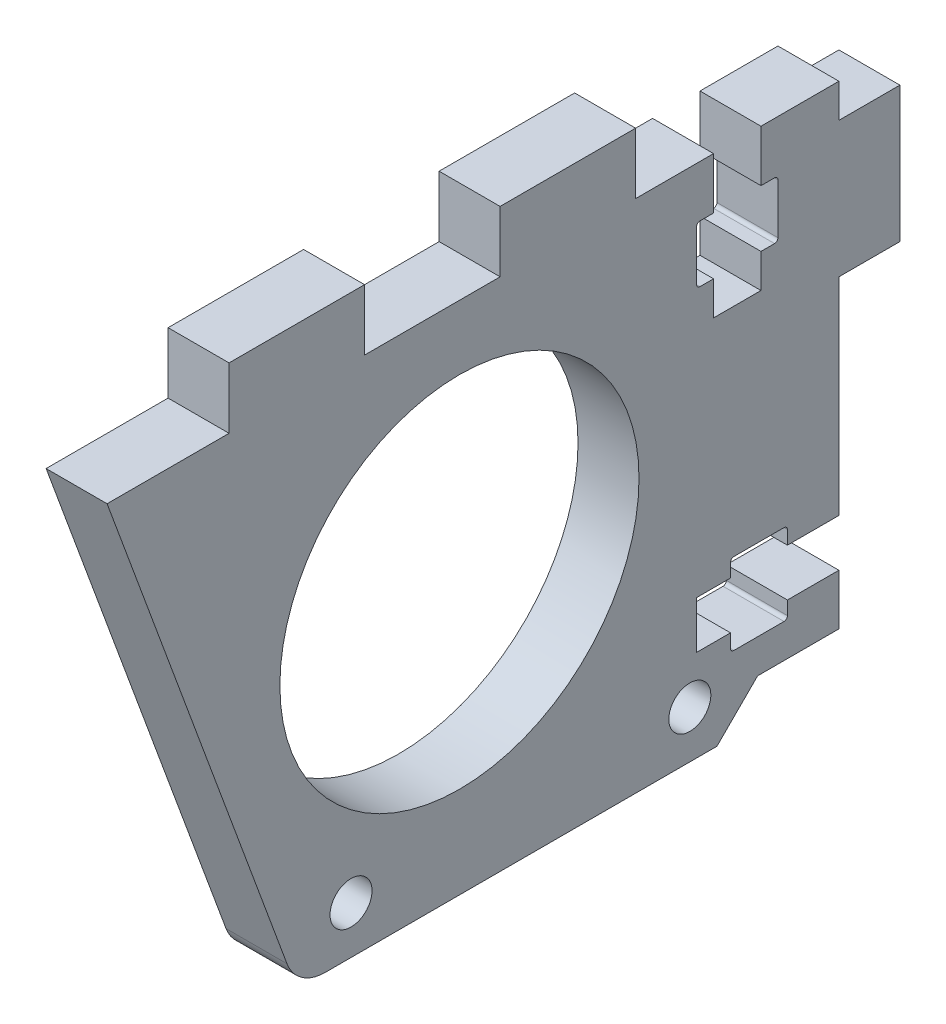
SolidWorks part; units mm, degrees
ref_plane "Front Plane" through (0, 0, 0) normal (0, 0, 1) x (1, 0, 0)
ref_plane "Top Plane" through (0, 0, 0) normal (0, 1, 0) x (1, 0, 0)
ref_plane "Right Plane" through (0, 0, 0) normal (1, 0, 0) x (0, 0, -1)
sketch "Sketch1" plane through (0, 0, 0) normal (1, 0, 0) x (0, 0, -1)
  line L0 (0, 0) -> (0, -35)
  line L1 (0, -35) -> (-54, 0)
  line L2 (-54, 0) -> (0, 0)
  dimension "D1" = 35
  dimension "D2" = 54
extrude "Boss-Extrude1" add sketch "Sketch1" along normal blind 4.5
sketch "Sketch2" plane through (4.5, 0, 0) normal (1, 0, 0) x (0, 0, -1)
  line L0 (0, -35) -> (0, 0) construction
  line L1 (-4.5, -2.5) -> (4.5, -2.5)
  line L2 (-4.5, -2.5) -> (-4.5, -12.5)
  line L3 (-4.5, -12.5) -> (4.5, -12.5)
  line L4 (4.5, -2.5) -> (4.5, -12.5)
  line L5 (-4.5, -2.5) -> (4.5, -12.5) construction
  line L6 (-4.5, -12.5) -> (4.5, -2.5) construction
  line L7 (0, 0) -> (-54, 0) construction
  point P0 (0, -7.5)
  dimension "D1" = 10
  dimension "D2" = 7.5
  dimension "D3" = 4.5
extrude "Boss-Extrude2" add sketch "Sketch2" against normal through all
sketch "Sketch3" plane through (4.5, 0, 0) normal (1, 0, 0) x (0, 0, -1)
  line L0 (0, -35) -> (-15, -35)
  line L1 (0, -25) -> (-54, 0)
  line L4 (0, -35) -> (0, -12.5) construction
  line L5 (0, -25) -> (0, -35)
  line L6 (-54, 0) -> (-15, -35)
  dimension "D1" = 15
  dimension "D2" = 10
extrude "Boss-Extrude3" add sketch "Sketch3" against normal through all
sketch "Sketch4" plane through (4.5, 0, 0) normal (1, 0, 0) x (0, 0, -1)
  line L0 (0, -29.5) -> (-10.5, -29.5) construction
  line L1 (0, -35) -> (0, -12.5) construction
  line L2 (0, -27.75) -> (-10.5, -27.75) construction
  line L3 (-10.5, -27.75) -> (-10.5, -31.25) construction
  line L4 (0, -31.25) -> (0, -27.75)
  line L5 (0, -27.75) -> (-3.8, -27.75)
  line L6 (-3.8, -27.75) -> (-3.8, -26.75)
  line L7 (-4.05, -26.5) -> (-7.75, -26.5)
  line L8 (-8, -26.75) -> (-8, -27.75)
  line L9 (-8, -27.75) -> (-10.5, -27.75)
  line L10 (-10.5, -27.75) -> (-10.5, -31.25)
  line L12 (0, -31.25) -> (-10.5, -31.25) construction
  line L13 (-8, -31.25) -> (-10.5, -31.25)
  line L14 (-8, -32.25) -> (-8, -31.25)
  line L15 (-4.05, -32.5) -> (-7.75, -32.5)
  line L16 (-3.8, -31.25) -> (-3.8, -32.25)
  line L17 (0, -31.25) -> (-3.8, -31.25)
  line L18 (4.5, -12.5) -> (4.5, -2.5) construction
  line L19 (0, -18.5) -> (-33.3857, -18.5) construction
  line L20 (-54, 0) -> (-15, -35) construction
  line L37 (0, -31.25) -> (-10.5, -31.25) construction
  arc A0 (-8, -32.25) -> (-7.75, -32.5) centre (-7.75, -32.25) ccw
  arc A1 (-4.05, -32.5) -> (-3.8, -32.25) centre (-4.05, -32.25) ccw
  arc A2 (-3.8, -26.75) -> (-4.05, -26.5) centre (-4.05, -26.75) ccw
  arc A3 (-7.75, -26.5) -> (-8, -26.75) centre (-7.75, -26.75) ccw
  point P10 (4.5, -7.5)
  point P20 (-8, -32.5)
  point P23 (-3.8, -32.5)
  point P26 (-3.8, -26.5)
  point P29 (-8, -26.5)
  dimension "D7" = 0.25
  dimension "D1" = 10.5
  dimension "D2" = 1.75
  dimension "D3" = 3
  dimension "D4" = 4.2
  dimension "D5" = 8
  dimension "D6" = 22
extrude "Cut-Extrude1" cut sketch "Sketch4" against normal through all
sketch "Sketch5" plane through (4.5, 0, 0) normal (1, 0, 0) x (0, 0, -1)
  line L0 (0, 0) -> (-54, 0) construction
  line L1 (-25, 4.5) -> (-15, 4.5)
  line L2 (-25, 4.5) -> (-25, 0)
  line L3 (0, 0) -> (-54, 0) construction
  line L4 (-15, 4.5) -> (-15, 0)
  line L5 (-25, 4.5) -> (-20, 0) construction
  line L6 (-20, 0) -> (-15, 4.5) construction
  line L7 (-30, 0) -> (-30, 4.5) construction
  line L8 (-40, 0) -> (-45, 4.5) construction
  line L9 (-35, 4.5) -> (-40, 0) construction
  line L10 (-45, 4.5) -> (-45, 0)
  line L12 (-35, 4.5) -> (-35, 0)
  line L13 (-35, 4.5) -> (-45, 4.5)
  line L14 (-20, 0) -> (-15, 4.5) construction
  line L15 (-15, 0) -> (-25, 0)
  line L16 (-35, 0) -> (-45, 0)
  point P0 (-20, 0)
  point P14 (-40, 0)
  dimension "D3" = 4.5
  dimension "D1" = 20
  dimension "D2" = 10
  dimension "D4" = 20
  dimension "D5" = 5
extrude "Boss-Extrude4" add sketch "Sketch5" against normal through all
sketch "Sketch8" [suppressed] plane through (4.5, 0, 0) normal (1, 0, 0) x (0, 0, -1)
  line L0 (-15, -30) -> (-27, -30) construction
  line L1 (-15, -35) -> (-27, -35)
  line L2 (-15, -25) -> (-27, -25)
  line L3 (-15, -35) -> (0, -35) construction
  line L4 (-15, -25) -> (-15, -35)
  arc A1 (-27, -25) -> (-27, -35) centre (-27, -30) ccw
  dimension "D5" = 5
  dimension "D1" = 0
  dimension "D2" = 12
  dimension "D3" = 0
  dimension "D4" = 10
extrude "Boss-Extrude5" [suppressed] add sketch "Sketch8" against normal up to surface (4.5 mm away) up to face at (0, -17.3125, 11.7125)
sketch "Sketch9" [suppressed] plane through (4.5, 0, 0) normal (1, 0, 0) x (0, 0, -1)
  line L0 (-27, -30) -> (-22, -30) construction
  line L1 (-27, -27) -> (-22, -27)
  line L2 (-27, -33) -> (-22, -33)
  arc A0 (-27, -27) -> (-27, -33) centre (-27, -30) ccw
  arc A1 (-22, -33) -> (-22, -27) centre (-22, -30) ccw
  point P3 (-24.5, -30)
  dimension "D1" = 3
  dimension "D2" = 5
extrude "Cut-Extrude3" [suppressed] cut sketch "Sketch9" against normal through all
sketch "Sketch10" plane through (0, 0, 0) normal (-1, 0, 0) x (0, 0, 1)
  line L0 (15, -35) -> (54, -12)
  line L1 (54, -12) -> (54, 0)
  line L3 (54, 0) -> (15, -35)
  dimension "D1" = 12
extrude "Boss-Extrude6" [suppressed] add sketch "Sketch10" against normal through all
sketch "Sketch6" plane through (4.5, 0, 0) normal (1, 0, 0) x (0, 0, -1)
  line L0 (-30, 0) -> (-30, -10.5) construction
  line L1 (-25, 0) -> (-35, 0) construction
  line L2 (-28.25, -10.5) -> (-31.75, -10.5) construction
  line L3 (-31.75, -10.5) -> (-31.75, 0) construction
  line L4 (-28.25, 0) -> (-31.75, 0)
  line L5 (-31.75, 0) -> (-31.75, -3.8)
  line L6 (-31.75, -3.8) -> (-32.75, -3.8)
  line L7 (-33, -4.05) -> (-33, -7.75)
  line L8 (-32.75, -8) -> (-31.75, -8)
  line L9 (-31.75, -8) -> (-31.75, -10.5)
  line L10 (-31.75, -10.5) -> (-28.25, -10.5)
  line L11 (-28.25, -10.5) -> (-28.25, 0) construction
  line L12 (-28.25, -8) -> (-28.25, -10.5)
  line L13 (-27.25, -8) -> (-28.25, -8)
  line L14 (-27, -4.05) -> (-27, -7.75)
  line L15 (-28.25, -3.8) -> (-27.25, -3.8)
  line L16 (-28.25, 0) -> (-28.25, -3.8)
  arc A0 (-33, -7.75) -> (-32.75, -8) centre (-32.75, -7.75) ccw
  arc A1 (-32.75, -3.8) -> (-33, -4.05) centre (-32.75, -4.05) ccw
  arc A2 (-27.25, -3.8) -> (-27, -4.05) centre (-27.25, -4.05) cw
  arc A3 (-27, -7.75) -> (-27.25, -8) centre (-27.25, -7.75) cw
  point P12 (-33, -8)
  point P15 (-33, -3.8)
  point P26 (-27, -3.8)
  point P27 (-27, -8)
  dimension "D1" = 10.5
  dimension "D2" = 1.75
  dimension "D4" = 4.2
  dimension "D6" = 0.25
  dimension "D3" = 8
  dimension "D5" = 3
extrude "Cut-Extrude2" [suppressed] cut sketch "Sketch6" against normal through all
sketch "Sketch11" plane through (0, 0, 0) normal (-1, 0, 0) x (0, 0, 1)
  line L0 (7.5, 0) -> (7.5, -10.5) construction
  line L1 (0, 0) -> (15, 0) construction
  line L2 (5.75, -10.5) -> (9.25, -10.5)
  line L3 (9.25, -10.5) -> (9.25, -8)
  line L4 (9.25, -8) -> (10.25, -8)
  line L5 (10.5, -7.75) -> (10.5, -4.05)
  line L6 (10.25, -3.8) -> (9.25, -3.8)
  line L7 (9.25, -3.8) -> (9.25, 0)
  line L8 (9.25, 0) -> (5.75, 0)
  line L9 (9.25, -8) -> (9.25, -3.8) construction
  line L10 (0, 0) -> (15, 0) construction
  line L11 (5.75, -8) -> (5.75, -3.8) construction
  line L12 (5.75, -3.8) -> (5.75, 0)
  line L13 (4.75, -3.8) -> (5.75, -3.8)
  line L14 (4.5, -7.75) -> (4.5, -4.05)
  line L15 (5.75, -8) -> (4.75, -8)
  line L16 (5.75, -10.5) -> (5.75, -8)
  arc A0 (10.5, -4.05) -> (10.25, -3.8) centre (10.25, -4.05) ccw
  arc A1 (4.75, -3.8) -> (4.5, -4.05) centre (4.75, -4.05) ccw
  arc A2 (10.25, -8) -> (10.5, -7.75) centre (10.25, -7.75) ccw
  arc A3 (4.5, -7.75) -> (4.75, -8) centre (4.75, -7.75) ccw
  point P11 (7.5, 0)
  point P22 (10.5, -3.8)
  point P25 (4.5, -3.8)
  point P28 (10.5, -8)
  point P31 (4.5, -8)
  dimension "D7" = 0.25
  dimension "D1" = 10.5
  dimension "D3" = 3
  dimension "D8" = 0.25
  dimension "D2" = 4.2
  dimension "D4" = 8
  dimension "D5" = 1.75
  dimension "D6" = 0
extrude "Cut-Extrude4" cut sketch "Sketch11" against normal through all
sketch "Sketch12" plane through (0, 0, 0) normal (-1, 0, 0) x (0, 0, 1)
  line L0 (28, -18) -> (16, -6) construction
  line L1 (28, -18) -> (28, -4.75) construction
  line L2 (28, -18) -> (40, -6) construction
  line L3 (28, -18) -> (14.75, -18) construction
  line L4 (28, -18) -> (16, -30) construction
  line L5 (28, -18) -> (16, -6) construction
  line L6 (0, -27.75) -> (0, -12.5) construction
  line L7 (25, 0) -> (35, 0) construction
  circle A0 centre (28, -18) radius 13.25
  circle A1 centre (16, -6) radius 1.55
  circle A2 centre (40, -6) radius 1.55
  circle A3 centre (16, -30) radius 1.55
  dimension "D1" = 26.5
  dimension "D2" = 3.1
  dimension "D3" = 12
  dimension "D4" = 45
  dimension "D5" = 28
  dimension "D6" = 18
extrude "Cut-Extrude5" [suppressed] cut sketch "Sketch12" against normal through all
sketch "Sketch13" [suppressed] plane through (0, 0, 0) normal (-1, 0, 0) x (0, 0, 1)
  line L0 (38.894, -10.458) -> (43.005, -7.6119)
  line L1 (19.9513, -28.5252) -> (16.914, -32.497)
  line L6 (28, -18) -> (54, 0) construction
  line L7 (28, -18) -> (15, -35) construction
  arc A0 (19.9513, -28.5252) -> (38.894, -10.458) centre (28, -18) ccw
  arc A1 (16.914, -32.497) -> (43.005, -7.6119) centre (28, -18) ccw
  arc A3 (40.0595, -12.5107) -> (21.2428, -29.3975) centre (28, -18) ccw construction
  dimension "D1" = 5
extrude "Boss-Extrude7" [suppressed] add sketch "Sketch13" against normal through all
sketch "Sketch14" [suppressed] plane through (0, 0, 0) normal (-1, 0, 0) x (0, 0, 1)
  line L0 (28, -4.75) -> (28, -31.25) construction
  line L1 (28, -18) -> (40, -30) construction
  circle A0 centre (28, -18) radius 13.25 construction
  circle A1 centre (40, -30) radius 3.5
  dimension "D2" = 7
  dimension "D1" = 45
  dimension "D3" = 12
extrude "Boss-Extrude8" [suppressed] add sketch "Sketch14" against normal through all
sketch "Sketch15" [suppressed] plane through (0, 0, 0) normal (-1, 0, 0) x (0, 0, 1)
  line L0 (42.4749, -32.4749) -> (28, -18) construction
  arc A0 (38.305, -33.0622) -> (43.0622, -28.305) centre (40, -30) ccw construction
  circle A1 centre (40, -30) radius 1.55
  dimension "D1" = 3.1
extrude "Cut-Extrude6" [suppressed] cut sketch "Sketch15" against normal through all
sketch "Sketch16" plane through (4.5, 0, 0) normal (1, 0, 0) x (0, 0, -1)
  line L0 (0, -34.5) -> (-39, -34.5) construction
  line L1 (0, -27.75) -> (0, -12.5) construction
  line L2 (-15, -34.5) -> (-39, -34.5) construction
  line L3 (-15, -38.5) -> (-39, -38.5)
  line L4 (-15, -30.5) -> (-39, -30.5)
  arc A0 (-15, -38.5) -> (-15, -30.5) centre (-15, -34.5) ccw
  arc A1 (-39, -30.5) -> (-39, -38.5) centre (-39, -34.5) ccw
  point P5 (-27, -34.5)
  point P12 (0, -20.125)
  dimension "D1" = 4
  dimension "D2" = 34.5
  dimension "D3" = 39
  dimension "D4" = 15
extrude "Boss-Extrude9" [suppressed] add sketch "Sketch16" against normal through all
sketch "Sketch17" [suppressed] plane through (4.5, 0, 0) normal (1, 0, 0) x (0, 0, -1)
  line L0 (-43, -34.5) -> (0, -34.5) construction
  line L1 (0, -27.75) -> (0, -12.5) construction
  line L2 (-26.5, -34.5) -> (-26.5, -20.0064) construction
  arc A0 (-42.1823, -32.0766) -> (-39, -38.5) centre (-39, -34.5) ccw construction
  circle A1 centre (-39, -34.5) radius 1.55
  circle A2 centre (-14, -34.5) radius 1.55
  dimension "D1" = 3.1
  dimension "D2" = 12.5
extrude "Cut-Extrude7" [suppressed] cut sketch "Sketch17" against normal through all
sketch "Sketch18" [suppressed] plane through (4.5, 0, 0) normal (1, 0, 0) x (0, 0, -1)
  line L0 (-15, -38.5) -> (0, -35)
  line L1 (0, -35) -> (-11.0314, -35)
  line L2 (-11.0314, -35) -> (-15, -38.5)
extrude "Boss-Extrude10" [suppressed] add sketch "Sketch18" against normal through all
sketch "Sketch20" plane through (4.5, 0, 0) normal (1, 0, 0) x (0, 0, -1)
  line L0 (0, -35) -> (0, -31.25) construction
  line L1 (-9, -38) -> (-37.9081, -38)
  line L2 (-40.7232, -36.0371) -> (-54, 0)
  line L3 (-54, 0) -> (-15, -35)
  line L4 (-15, -35) -> (-6, -35)
  line L5 (-9, -38) -> (-6, -35)
  line L6 (-40.7232, -36.0371) -> (-40, -38) construction
  line L7 (-40, -38) -> (-37.9081, -38) construction
  arc A1 (-37.9081, -38) -> (-40.7232, -36.0371) centre (-37.9081, -35) cw
  point P0 (0, -33.125)
  point P14 (-40, -38)
  dimension "D3" = 6
  dimension "D4" = 3
  dimension "D1" = 40
  dimension "D2" = 3
  dimension "D5" = 135
extrude "Boss-Extrude11" add sketch "Sketch20" against normal through all
sketch "Sketch21" plane through (4.5, 0, 0) normal (1, 0, 0) x (0, 0, -1)
  line L0 (0, -34.5) -> (-41.2895, -34.5) construction
  line L1 (0, -35) -> (0, -31.25) construction
  line L2 (-54, 0) -> (-40.7232, -36.0371) construction
  line L3 (0, -27.75) -> (0, -12.5) construction
  circle A0 centre (-36, -34.5) radius 1.55
  circle A1 centre (-11, -34.5) radius 1.55
  dimension "D2" = 3.1
  dimension "D3" = 3.1
  dimension "D1" = 25
  dimension "D4" = 34.5
  dimension "D5" = 11
extrude "Cut-Extrude8" cut sketch "Sketch21" against normal through all
sketch "Sketch22" plane through (4.5, 0, 0) normal (1, 0, 0) x (0, 0, -1)
  line L0 (0, -27.75) -> (0, -12.5) construction
  line L1 (-25, 0) -> (-35, 0) construction
  circle A0 centre (-28, -18) radius 13.25
  dimension "D2" = 18
  dimension "D3" = 26.5
  dimension "D1" = 28
extrude "Cut-Extrude9" cut sketch "Sketch22" against normal through all
equation "\"X-ROD-SPACING\"=45"
equation "\"Y-ROD-SPACING\"=75"
equation "\"Z-ROD-SPACING\"=17.5"
equation "\"Y-BED-OFFSET\"=2"
equation "\"Y-BED-ROD-INSET\"=3.5"
equation "\"Y-BED-SCREW-SPACING\"=209"
equation "\"Y-BED-SCREW-CUTOUT-SLOT-HEIGHT\"=2"
equation "\"T-SLOT-NUT-FILLET-RADIUS\"=0.25"
equation "\"T-SLOT-SCREW-SHAFT-RADIUS\"=1.75"
equation "\"T-SLOT-SCREW-SHAFT-CUTOUT-LENGTH\"=10.5"
equation "\"T-SLOT-NUT-DEPTH\"=4.2"
equation "\"T-SLOT-NUT-WIDTH\"=3"
equation "\"T-SLOT-NUT-END-DISTANCE\"=8"
equation "\"ACRYLIC-THICKNESS\"=10"
equation "\"ACRYLIC-THICKNESS2\"=4.5"
equation "\"ACRYLIC-TAB-CUTOUT-SIZE\"=\"ACRYLIC-THICKNESS\"+\"ACRYLIC-TAB-TOLERANCE\"*2"
equation "\"ACRYLIC-TAB-WIDTH\"=\"ACRYLIC-THICKNESS\""
equation "\"ACRYLIC-M3-HOLE\"=3.1"
equation "\"SMOOTHROD-CAP-SCREW-DISTANCE\"=20"
equation "\"FRAME-WIDTH-INNER\"=370"
equation "\"NEMA17-HOLE-SPACING\"=31"
equation "\"NEMA17-CENTRAL-CUTOUT\"=22.5"
equation "\"Z-BRACKET-REACH\"=55"
equation "\"Z-ROD-INSET\"=16"
equation "\"TOP-BRACKET-SPACING\"=40"
equation "\"SMOOTHROD-X-LENGTH\"=350"
equation "\"SMOOTHROD-Y-LENGTH\"=350"
equation "\"SMOOTHROD-Z-LENGTH\"=350"
equation "\"SMOOTHROD-TIGHTENING-HEADROOM\"=.25"
equation "\"LEADSCREW-Z-LENGTH\"=300"
equation "\"SCREW-LENGTH-FRAME\"=\"ACRYLIC-THICKNESS\" + 10"
equation "\"SCREW-LENGTH-MOTOR\"=\"ACRYLIC-THICKNESS\" + 5"
equation "\"SCREW-LENGTH-EXTRUDER\"=28"
equation "\"SCREW-HEAD-RADIUS\"=6"
equation "\"PRINTED-X-SMOOTHROD-DIAMETER\"=8.2"
equation "\"PRINTED-X-SMOOTHROD-CUTOUT\"=10"
equation "\"PRINTED-X-BASE-HEIGHT\"=10"
equation "\"PRINTED-LM8UU-CUTOUT-SIZE\"=15.25"
equation "\"PRINTED-LM8UU-CUTOUT-LENGTH\"=24.5"
equation "\"PRINTED-X-IDLER-HEIGHT\"=16"
equation "\"PSU-MOUNTING-WIDTH\"=95"
equation "\"PSU-MOUNTING-HEIGHT\"=177"
equation "\"Y-BELT-TO-ROD-DISTANCE\"=20"
equation "\"SPOOL-HOLDER-ROD-SPACING\"=150"
equation "\"ACRYLIC-X-CARRIAGE-WIDTH\"=55"
equation "\"ACRYLIC-X-CARRIAGE-HEIGHT\"=75"
equation "\"ACRYLIC-X-CARRIAGE-SCREW-SPACING-X\"=15"
equation "\"ACRYLIC-X-CARRIAGE-SCREW-SPACING-Y\"=33"
equation "\"ACRYLIC-X-CARRIAGE-CENTER-TAB-SPACING\"=14"
equation "\"ACRYLIC-X-CARRIAGE-EXTRUDER-SHELF-DEPTH\"=\"ACRYLIC-X-CARRIAGE-EXTRUDER-OFFSET\" + 28"
equation "\"D2@Sketch1\"=\"ACRYLIC-X-CARRIAGE-EXTRUDER-SHELF-DEPTH\""
equation "\"D1@Boss-Extrude1\"=\"ACRYLIC-THICKNESS2\""
equation "\"D1@Sketch2\"=\"ACRYLIC-TAB-WIDTH\""
equation "\"D3@Sketch2\"=\"ACRYLIC-THICKNESS2\""
equation "\"ACRYLIC-X-CARRIAGE-LM8UU-CUTOUT-WIDTH\"=24.25"
equation "\"ACRYLIC-X-CARRIAGE-EXTRUDER-BRACE-SPACING\"=23"
equation "\"ACRYLIC-X-CARRIAGE-EXTRUDER-BRACE-HEIGHT\"=35"
equation "\"D1@Sketch1\"=\"ACRYLIC-X-CARRIAGE-EXTRUDER-BRACE-HEIGHT\""
equation "\"D1@Sketch4\"=\"T-SLOT-SCREW-SHAFT-CUTOUT-LENGTH\""
equation "\"D2@Sketch4\"=\"T-SLOT-SCREW-SHAFT-RADIUS\""
equation "\"D3@Sketch4\"=\"T-SLOT-NUT-WIDTH\""
equation "\"D4@Sketch4\"=\"T-SLOT-NUT-DEPTH\""
equation "\"D5@Sketch4\"=\"T-SLOT-NUT-END-DISTANCE\""
equation "\"D7@Sketch4\"=\"T-SLOT-NUT-FILLET-RADIUS\""
equation "\"ACRYLIC-X-CARRIAGE-EXTRUDER-BRACE-SCREW-SPACING\"=22"
equation "\"D6@Sketch4\"=\"ACRYLIC-X-CARRIAGE-EXTRUDER-BRACE-SCREW-SPACING\""
equation "\"ACRYLIC-X-CARRIAGE-EXTRUDER-BRACE-TAB-OFFSET\"=20"
equation "\"D1@Sketch5\"=\"ACRYLIC-X-CARRIAGE-EXTRUDER-BRACE-TAB-OFFSET\""
equation "\"D2@Sketch5\"=\"ACRYLIC-TAB-WIDTH\""
equation "\"D3@Sketch5\"=\"ACRYLIC-THICKNESS2\""
equation "\"ACRYLIC-X-CARRIAGE-EXTRUDER-OFFSET\"=26"
equation "\"ACRYLIC-X-CARRIAGE-EXTRUDER-ANGLE\"=90"
equation "\"D1@Sketch6\"=\"T-SLOT-SCREW-SHAFT-CUTOUT-LENGTH\""
equation "\"D2@Sketch6\"=\"T-SLOT-SCREW-SHAFT-RADIUS\""
equation "\"D3@Sketch6\"=\"T-SLOT-NUT-END-DISTANCE\""
equation "\"D4@Sketch6\"=\"T-SLOT-NUT-DEPTH\""
equation "\"D5@Sketch6\"=\"T-SLOT-NUT-WIDTH\""
equation "\"D6@Sketch6\"=\"T-SLOT-NUT-FILLET-RADIUS\""
equation "\"D1@Sketch11\"=\"T-SLOT-SCREW-SHAFT-CUTOUT-LENGTH\""
equation "\"D2@Sketch11\"=\"T-SLOT-NUT-DEPTH\""
equation "\"D3@Sketch11\"=\"T-SLOT-NUT-WIDTH\""
equation "\"D4@Sketch11\"=\"T-SLOT-NUT-END-DISTANCE\""
equation "\"D5@Sketch11\"=\"T-SLOT-SCREW-SHAFT-RADIUS\""
equation "\"D7@Sketch11\"=\"T-SLOT-NUT-FILLET-RADIUS\""
equation "\"D8@Sketch11\"=\"T-SLOT-NUT-FILLET-RADIUS\""
equation "\"D2@Sketch12\"=\"ACRYLIC-M3-HOLE\""
equation "\"D1@Sketch15\"=\"ACRYLIC-M3-HOLE\""
equation "\"D1@Sketch17\"=\"ACRYLIC-M3-HOLE\""
equation "\"D2@Sketch21\"=\"ACRYLIC-M3-HOLE\""
equation "\"D3@Sketch21\"=\"ACRYLIC-M3-HOLE\""
